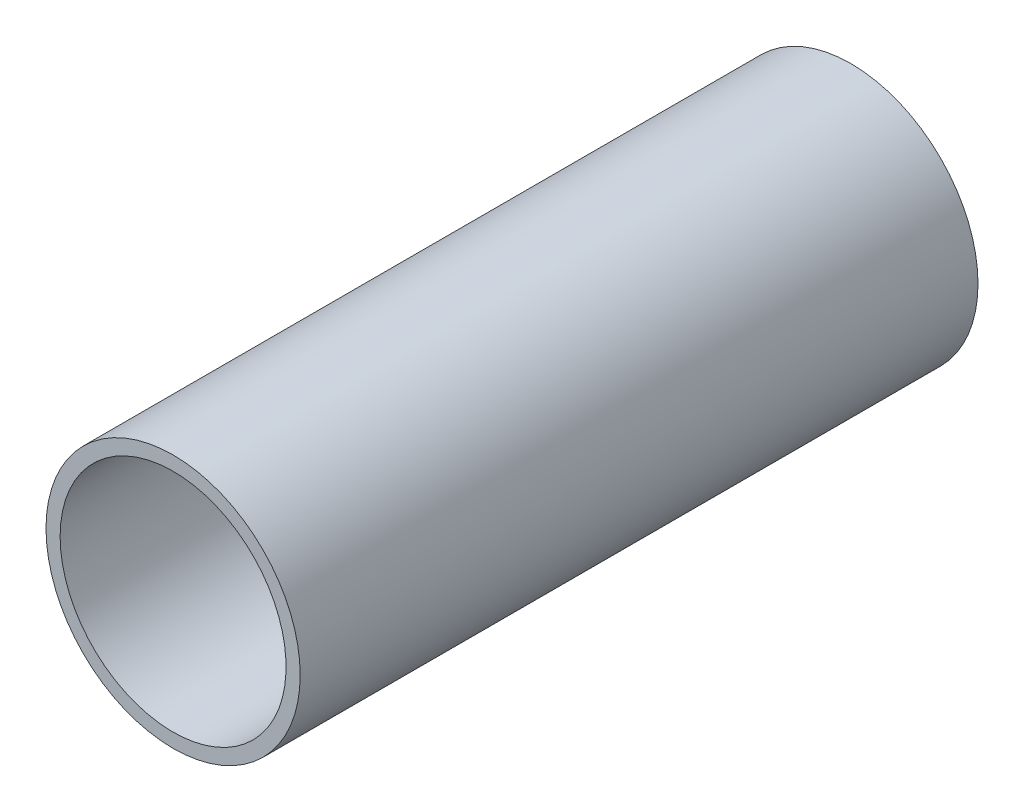
SolidWorks part; units mm, degrees
material "ABS PC"
ref_plane "Front Plane" through (0, 0, 0) normal (0, 0, 1) x (1, 0, 0)
ref_plane "Top Plane" through (0, 0, 0) normal (0, 1, 0) x (1, 0, 0)
ref_plane "Right Plane" through (0, 0, 0) normal (1, 0, 0) x (0, 0, -1)
sketch "Sketch1" plane through (0, 0, 0) normal (0, 0, 1) x (1, 0, 0)
  circle A0 centre (0, 0) radius 57.15
  circle A1 centre (0, 0) radius 50.8
  dimension "D1" = 114.3
  dimension "D2" = 101.6
extrude "Boss-Extrude1" add sketch "Sketch1" along normal mid plane 304.8
